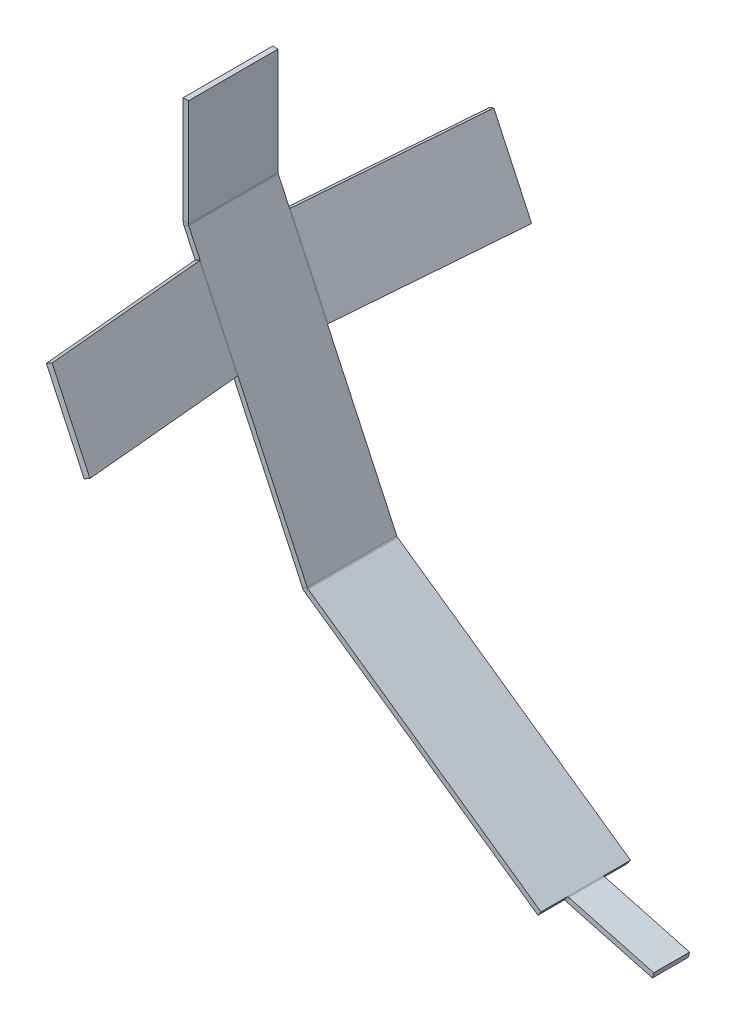
SolidWorks part; units mm, degrees
note: The reader was unsure of these and kept them because the rebuilt part matched: flange length of "Edge-Flange1", "Edge-Flange2", "Edge-Flange3", "Edge-Flange4".
ref_plane "Front Plane" through (0, 0, 0) normal (0, 0, 1) x (1, 0, 0)
ref_plane "Top Plane" through (0, 0, 0) normal (0, 1, 0) x (1, 0, 0)
ref_plane "Right Plane" through (0, 0, 0) normal (1, 0, 0) x (0, 0, -1)
sketch "Sketch1" plane through (0, 0, 0) normal (1, 0, 0) x (0, 0, -1)
  line L1 (-12.5, -15) -> (12.5, -15)
  line L2 (-12.5, -15) -> (-12.5, 15)
  line L3 (-12.5, 15) -> (12.5, 15)
  line L4 (12.5, -15) -> (12.5, 15)
  line L5 (-12.5, -15) -> (12.5, 15) construction
  line L6 (-12.5, 15) -> (12.5, -15) construction
  point P0 (0, 0)
  dimension "D1" = 25
  dimension "D2" = 30
base flange "Base-Flange1" sketch "Sketch1" thickness 1.5 reverse thickness direction yes parameters "D1"=0.7366
edge flange "Edge-Flange1" sketch "Sketch8" flange angle 155 flange length 79 flange position material outside bend radius 0.7366 thickness 1.5 relief rectangular parameters "D6"=10
sketch "Sketch8" plane through (1.5, -15, 0) normal (-0.9063, -0.4226, 0) x (0, 0, -1)
  line L0 (-12.5, 0) -> (12.5, 0) construction
  line L1 (-12.5, 0) -> (12.5, 0)
  line L2 (-12.5, 0) -> (-12.5, 78.6675)
  line L3 (-12.5, 78.6675) -> (12.5, 78.6675)
  line L4 (12.5, 78.6675) -> (12.5, 0)
bend "EdgeBend1" bend radius 0.7366 bend angle 25 parameters "D5"=1
edge flange "Edge-Flange2" sketch "Sketch11" flange angle 150 flange length 80 flange position material outside bend radius 0.7366 thickness 1.5 relief rectangular parameters "D6"=10
sketch "Sketch11" plane through (34.7463, -86.2969, 0) normal (-0.5736, -0.8192, 0) x (0, 0, -1)
  line L2 (-12.5, 0) -> (-12.5, 79.5981)
  line L3 (-12.5, 79.5981) -> (12.5, 79.5981)
  line L4 (12.5, 79.5981) -> (12.5, 0)
  line L7 (12.5, 0) -> (-12.5, 0) construction
  line L8 (12.5, 0) -> (-12.5, 0)
bend "EdgeBend2" bend radius 0.7366 bend angle 30 parameters "D5"=2
edge flange "Edge-Flange3" sketch "Sketch14" flange angle 160 flange length 25 flange position bend outside bend radius 0.7366 thickness 1.5 relief rectangular parameters "D6"=10
sketch "Sketch14" plane through (99.9492, -131.9525, 0) normal (-0.2588, -0.9659, 0) x (0, 0, -1)
  line L2 (-5, 0) -> (-5, 24.7355)
  line L3 (-5, 24.7355) -> (5, 24.7355)
  line L4 (5, 24.7355) -> (5, 0)
  line L7 (12.5, 0) -> (-12.5, 0) construction
  line L8 (5, 0) -> (-5, 0)
  line L9 (-12.5, 0) -> (-12.5, -74.6123) construction
  dimension "D1" = 10
  dimension "D2" = 7.5
bend "EdgeBend3" bend radius 0.7366 bend angle 20 parameters "D5"=3
edge flange "Edge-Flange4" sketch "Sketch19" flange profiles "Sketch19", "Sketch20" flange angle 170 flange length 50 flange position bend outside bend radius 0.7366 thickness 1.5 relief rectangular parameters "D6"=10, "D8"=1
sketch "Sketch19" plane through (-4.5132, -2.1046, 12.5) normal (-0.8925, -0.4162, 0.1736) x (0.4226, -0.9063, 0)
  line L2 (21.8918, 0) -> (21.8918, 49.8688)
  line L3 (21.8918, 49.8688) -> (46.8918, 49.8688)
  line L4 (46.8918, 49.8688) -> (46.8918, 0)
  line L7 (92.6986, 0) -> (14.3918, 0) construction
  line L8 (46.8918, 0) -> (21.8918, 0)
  line L9 (14.3918, 0) -> (14.3918, -24.6202) construction
  dimension "D1" = 25
  dimension "D2" = 7.5
sketch "Sketch20" plane through (-4.5132, -2.1046, -12.5) normal (-0.8925, -0.4162, -0.1736) x (-0.4226, 0.9063, 0)
  line L0 (-14.3918, 0) -> (-92.6986, 0) construction
  line L1 (-21.8918, 0) -> (-46.8918, 0)
  line L2 (-46.8918, 0) -> (-46.8918, 49.8688)
  line L3 (-46.8918, 49.8688) -> (-21.8918, 49.8688)
  line L4 (-21.8918, 49.8688) -> (-21.8918, 0)
  line L5 (-14.3918, -24.6202) -> (-14.3918, 0) construction
  dimension "D1" = 25
  dimension "D2" = 7.5
bend "EdgeBend4" bend radius 0.7366 bend angle 10 parameters "D5"=4
bend "EdgeBend5" bend radius 0.7366 bend angle 10 parameters "D5"=5
sketch "Bend-Lines1" [suppressed] plane through (0, 0, 0) normal (0, 1, 0) x (1, 0, 0)
sketch "Bounding-Box1" [suppressed] plane through (0, 0, 0) normal (0, 1, 0) x (1, 0, 0)
sheet metal parameters "Sheet-Metal1" thickness 1.5 parameters "D1"=0.7366
flat pattern "Flat-Pattern1" [suppressed]
sketch "Bend-Lines2" plane through (0, 0, 0) normal (0, 1, 0) x (1, 0, 0)
sketch3d "Bounding-Box2" [suppressed]
  line L0 (-12.5, 22.5, 0) -> (-12.5, -22.5, 0) construction
  line L1 (12.5, 22.5, 0) -> (12.5, -22.5, 0) construction
  line L2 (-12.5, 22.5, 0) -> (12.5, 22.5, 0) construction
  line L3 (-12.5, -22.5, 0) -> (12.5, -22.5, 0) construction
sheet metal parameters "Sheet-Metal2" thickness 1.5 parameters "D1"=0.7366
flat pattern "Flat-Pattern1"
sketch "Bend-Lines2" plane through (0, 0, 0) normal (-1, 0, 0) x (0, 0, 1)
  line L0 (-12.5, -22.661) -> (12.5, -22.661) construction
  line L1 (-12.5, -22.661) -> (12.5, -22.661) construction
sketch3d "Bounding-Box2" [suppressed]
  line L0 (12.5, 22.5, 0) -> (12.5, -102.4895, 0) construction
  line L1 (-12.5, 22.5, 0) -> (-12.5, -102.4895, 0) construction
  line L2 (12.5, 22.5, 0) -> (-12.5, 22.5, 0) construction
  line L3 (12.5, -102.4895, 0) -> (-12.5, -102.4895, 0) construction
bend of the flat pattern "Flatten-<EdgeBend1>1"
sheet metal parameters "Sheet-Metal3" thickness 1.5 parameters "D1"=0.7366
flat pattern "Flat-Pattern1"
sketch "Bend-Lines2" plane through (0, 0, 0) normal (-1, 0, 0) x (0, 0, 1)
  line L0 (-12.5, -22.661) -> (12.5, -22.661) construction
  line L1 (-12.5, -22.661) -> (12.5, -22.661) construction
  line L2 (-12.5, -102.6813) -> (12.5, -102.6813) construction
  line L3 (-12.5, -102.6813) -> (12.5, -102.6813) construction
sketch3d "Bounding-Box2" [suppressed]
  line L0 (12.5, 22.5, 0) -> (12.5, -172.4712, 0) construction
  line L1 (-12.5, 22.5, 0) -> (-12.5, -172.4712, 0) construction
  line L2 (12.5, 22.5, 0) -> (-12.5, 22.5, 0) construction
  line L3 (12.5, -172.4712, 0) -> (-12.5, -172.4712, 0) construction
bend of the flat pattern "Flatten-<EdgeBend1>1"
bend of the flat pattern "Flatten-<EdgeBend2>1"
sheet metal parameters "Sheet-Metal4" thickness 1.5 parameters "D1"=0.7366
flat pattern "Flat-Pattern1"
sketch "Bend-Lines2" plane through (0, 0, 0) normal (-1, 0, 0) x (0, 0, 1)
  line L0 (-12.5, -15.161) -> (12.5, -15.161) construction
  line L1 (-12.5, -15.161) -> (12.5, -15.161) construction
  line L2 (-12.5, -94.1813) -> (12.5, -94.1813) construction
  line L3 (-12.5, -94.1813) -> (12.5, -94.1813) construction
  line L4 (-5, -174.2307) -> (5, -174.2307) construction
  line L5 (-5, -174.2307) -> (5, -174.2307) construction
sketch3d "Bounding-Box2" [suppressed]
  line L0 (12.5, 15, 0) -> (12.5, -199.0958, 0) construction
  line L1 (-12.5, 15, 0) -> (-12.5, -199.0958, 0) construction
  line L2 (12.5, 15, 0) -> (-12.5, 15, 0) construction
  line L3 (12.5, -199.0958, 0) -> (-12.5, -199.0958, 0) construction
bend of the flat pattern "Flatten-<EdgeBend1>1"
bend of the flat pattern "Flatten-<EdgeBend2>1"
bend of the flat pattern "Flatten-<EdgeBend3>1"
sheet metal parameters "Sheet-Metal5" thickness 1.5 parameters "D1"=0.7366
flat pattern "Flat-Pattern1"
sketch "Bend-Lines2" plane through (0, 0, 0) normal (-1, 0, 0) x (0, 0, 1)
  line L0 (-12.5, -15.161) -> (12.5, -15.161) construction
  line L1 (-12.5, -15.161) -> (12.5, -15.161) construction
  line L2 (-12.5, -94.1813) -> (12.5, -94.1813) construction
  line L3 (-12.5, -94.1813) -> (12.5, -94.1813) construction
  line L4 (-5, -174.2307) -> (5, -174.2307) construction
  line L5 (-5, -174.2307) -> (5, -174.2307) construction
  line L6 (-12.6297, -15.4854) -> (-12.6297, -40.4854) construction
  line L7 (12.6297, -40.4854) -> (12.6297, -15.4854) construction
  line L8 (-12.6297, -15.4854) -> (-12.6297, -40.4854) construction
  line L9 (12.6297, -40.4854) -> (12.6297, -15.4854) construction
sketch3d "Bounding-Box2" [suppressed]
  line L0 (44.0512, 35.5239, 0) -> (114.7456, -159.2663, 0) construction
  line L1 (-74.5305, -7.5125, 0) -> (-3.8361, -202.3026, 0) construction
  line L2 (44.0512, 35.5239, 0) -> (-74.5305, -7.5125, 0) construction
  line L3 (114.7456, -159.2663, 0) -> (-3.8361, -202.3026, 0) construction
bend of the flat pattern "Flatten-<EdgeBend1>1"
bend of the flat pattern "Flatten-<EdgeBend2>1"
bend of the flat pattern "Flatten-<EdgeBend3>1"
bend of the flat pattern "Flatten-<EdgeBend4>1"
bend of the flat pattern "Flatten-<EdgeBend5>1"
